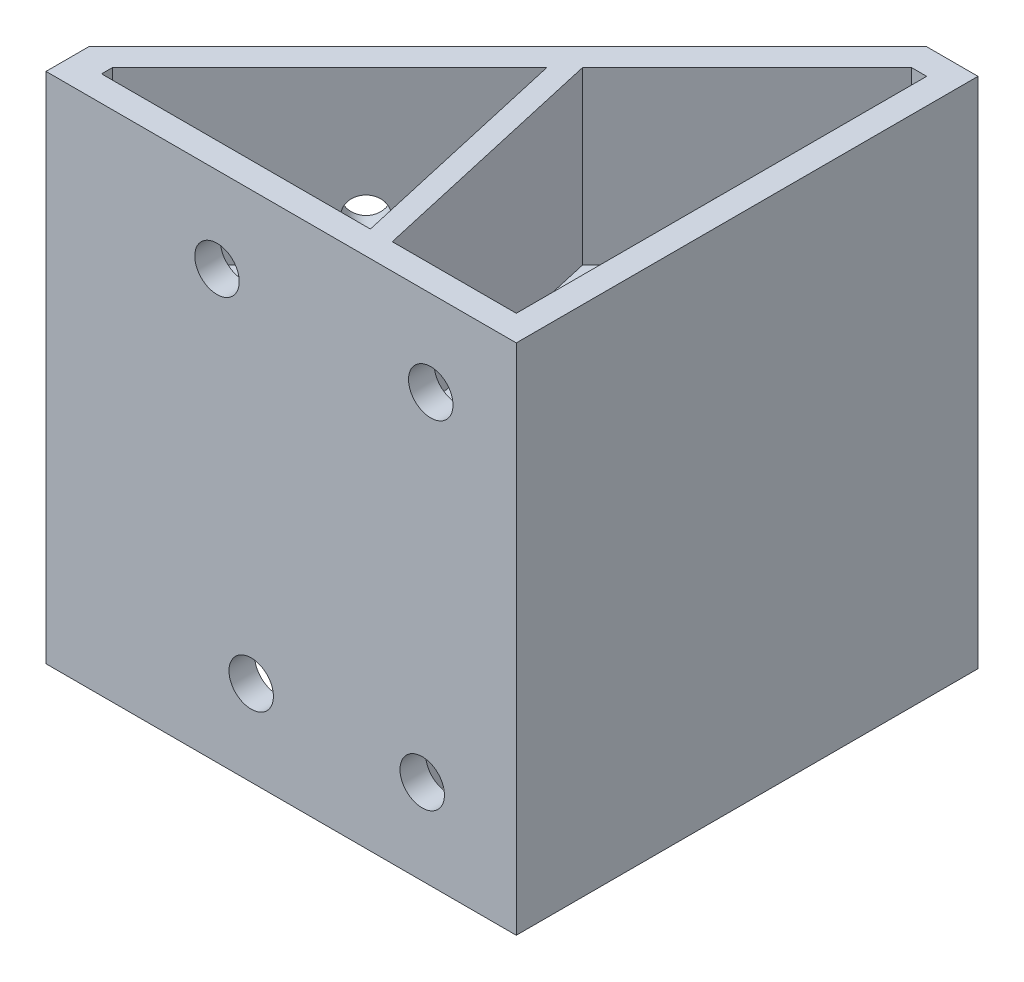
SolidWorks part; units mm, degrees
ref_plane "前视基准面" through (0, 0, 0) normal (0, 0, 1) x (1, 0, 0)
ref_plane "上视基准面" through (0, 0, 0) normal (0, 1, 0) x (1, 0, 0)
ref_plane "右视基准面" through (0, 0, 0) normal (1, 0, 0) x (0, 0, -1)
sketch "草图1" plane through (0, 0, 0) normal (0, 1, 0) x (1, 0, 0)
  line L0 (0, 0) -> (-55, 0)
  line L1 (-55, 5) -> (-6, 54)
  line L3 (-4.7574, 51) -> (-51.5, 4.2574)
  line L4 (-51.5, 3) -> (-3, 3)
  line L6 (-6, 54) -> (0, 54)
  line L7 (0, 54) -> (0, 0)
  line L9 (-3, 51) -> (-3, 3)
  line L10 (-4.7574, 51) -> (-3, 51)
  line L11 (-55, 0) -> (-55, 5)
  line L12 (-51.5, 3) -> (-51.5, 4.2574)
  dimension "D1" = 45
  dimension "D2" = 3
  dimension "D3" = 3
  dimension "D4" = 3.5
  dimension "D5" = 3
  dimension "D6" = 6
  dimension "D7" = 54
  dimension "D8" = 3
  dimension "D9" = 55
extrude "凸台-拉伸1" add sketch "草图1" along normal blind 60
ref_plane "基准面1" through (0, 30, 0) normal (0, 1, 0) x (1, 0, 0)
sketch "草图3" plane through (0, 0, -3) normal (0, 0, -1) x (-1, 0, 0)
  line L0 (6, 0) -> (55, 0) construction
  line L1 (6, 60) -> (6, 0) construction
  line L3 (6, 60) -> (55, 60) construction
  circle A0 centre (11, 10) radius 2.6
  circle A1 centre (31, 10) radius 2.6
  circle A2 centre (35, 50) radius 2.6
  circle A3 centre (10, 50) radius 2.6
  dimension "D1" = 10
  dimension "D2" = 5.2
  dimension "D3" = 5.2
  dimension "D4" = 20
  dimension "D5" = 5
  dimension "D6" = 5.2
  dimension "D7" = 5.2
  dimension "D8" = 25
  dimension "D9" = 10
extrude "切除-拉伸1" cut sketch "草图3" against normal blind 10
sketch "草图4" plane through (-30, 0, -30) normal (-0.7071, 0, -0.7071) x (-0.7071, 0, 0.7071)
  line L1 (42.4264, 30) -> (-53.6604, 30) construction
  line L2 (29.7, 30) -> (-29.7, 30) construction
  line L3 (42.4264, 60) -> (42.4264, 0) construction
  circle A0 centre (12.4264, 45) radius 2.1
  circle A1 centre (-17.5736, 45) radius 2.1
  circle A2 centre (12.4264, 15) radius 2.1
  circle A3 centre (-17.5736, 15) radius 2.1
  dimension "D1" = 4.2
  dimension "D2" = 30
  dimension "D3" = 30
  dimension "D4" = 30
  dimension "D5" = 4.2
extrude "切除-拉伸2" cut sketch "草图4" against normal blind 10
sketch "草图6" plane through (0, 0, -3) normal (0, 0, -1) x (-1, 0, 0)
  circle A0 centre (31, 10) radius 4.5
  circle A1 centre (35, 50) radius 4.5
  dimension "D1" = 9
  dimension "D2" = 9
ref_plane "基准面2" through (0, 0, -18) normal (0, 0, -1) x (-1, 0, 0)
ref_axis "基准轴1" through (-31, 10, 1) along (0, 0, -1)
ref_plane "基准面3" through (0, 20, 0) normal (0, -1, 0) x (-1, 0, 0)
sketch "草图7" plane through (0, 20, 0) normal (0, -1, 0) x (-1, 0, 0)
  line L0 (3, 52.7574) -> (51.5, 4.2574)
  line L1 (3, 3) -> (3, 51) construction
  line L2 (4.7574, 51) -> (51.5, 4.2574) construction
  line L3 (51.5, 3) -> (3, 3)
  line L4 (3, 3) -> (3, 52.7574)
  line L5 (51.5, 4.2574) -> (51.5, 3)
extrude "凸台-拉伸2" add sketch "草图7" against normal blind 3
ref_plane "基准面4" through (0, 40, 0) normal (0, 1, 0) x (1, 0, 0)
sketch "草图8" plane through (0, 40, 0) normal (0, 1, 0) x (1, 0, 0)
  line L7 (-3, 51) -> (-4.7574, 51)
  line L8 (-4.7574, 51) -> (-51.5, 4.2574)
  line L9 (-51.5, 3) -> (-3, 3)
  line L10 (-3, 3) -> (-3, 51)
  line L11 (-3, 51) -> (-4.7574, 51)
  line L12 (-4.7574, 51) -> (-51.5, 4.2574)
  line L13 (-51.5, 3) -> (-3, 3)
  line L14 (-3, 3) -> (-3, 51)
  line L16 (-51.5, 4.2574) -> (-51.5, 3)
  line L17 (-51.5, 4.2574) -> (-51.5, 3)
  dimension "D1" = 0
extrude "凸台-拉伸3" add sketch "草图8" against normal blind 3
sketch "草图9" plane through (0, 0, 0) normal (0, -1, 0) x (1, 0, 0)
  line L0 (-20.0633, -3) -> (-26.0984, -29.659)
  line L1 (-51.5, -3) -> (-3, -3) construction
  line L2 (-4.7574, -51) -> (-51.5, -4.2574) construction
  line L5 (-24.0083, -31.7491) -> (-17.5, -3)
  line L6 (-3, -3) -> (-51.5, -3) construction
  line L7 (-17.5, -3) -> (-20.0633, -3)
  line L8 (-10.5, 3.9564) -> (-10.5, -9.2261) construction
  line L9 (-12.6, 0) -> (-12.6, -3) construction
  line L10 (-8.4, -3) -> (-8.4, 0) construction
  line L11 (-16.9372, -38.8202) -> (-19.0585, -40.9415) construction
  line L12 (-24.0083, -31.7491) -> (-26.0984, -29.659)
  dimension "D1" = 10
  dimension "D2" = 7
  dimension "D3" = 2.5
extrude "凸台-拉伸4" add sketch "草图9" against normal up to surface (20 mm away) up to face at (-22.7515, 20, -22.4515)
sketch "草图10" plane through (0, 60, 0) normal (0, 1, 0) x (1, 0, 0)
  line L0 (-26.0984, 29.659) -> (-24.0083, 31.7491)
  line L1 (-24.0083, 31.7491) -> (-17.5, 3)
  line L2 (-17.5, 3) -> (-20.0633, 3)
  line L3 (-20.0633, 3) -> (-26.0984, 29.659)
extrude "凸台-拉伸5" add sketch "草图10" against normal up to surface (20 mm away) up to face at (-22.7515, 40, -22.4515)
sketch "草图11" plane through (-30, 0, -30) normal (-0.7071, 0, -0.7071) x (-0.7071, 0, 0.7071)
  line L0 (-17.5736, 45) -> (12.4264, 45) construction
  line L1 (-17.5736, 15) -> (12.4264, 15) construction
  line L3 (-14.5736, 47) -> (9.4264, 47)
  line L4 (-14.5736, 47) -> (-14.5736, 43)
  line L5 (-14.5736, 43) -> (9.4264, 43)
  line L6 (9.4264, 47) -> (9.4264, 43)
  line L7 (-13.7955, 17) -> (8.3896, 17)
  line L8 (-13.7955, 17) -> (-13.7955, 13)
  line L9 (-13.7955, 13) -> (8.3896, 13)
  line L10 (8.3896, 17) -> (8.3896, 13)
  dimension "D1" = 4
  dimension "D2" = 4
  dimension "D3" = 3
  dimension "D4" = 3
extrude "凸台-拉伸6" add sketch "草图11" along normal blind 2
ref_axis "基准轴2" through (-35.1806, 15, -17.607) along (-0.7071, 0, -0.7071)
